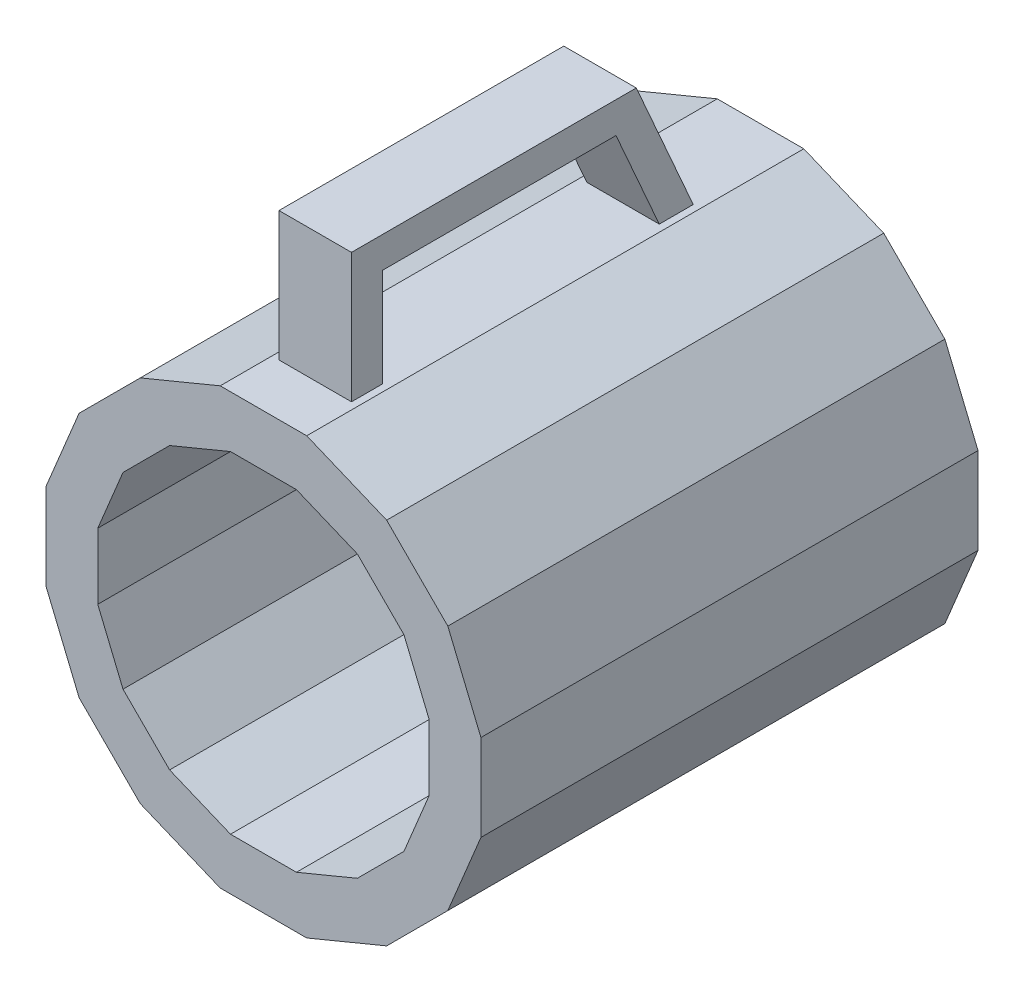
SolidWorks part; units mm, degrees
material "1060 Alloy"
ref_plane "Front Plane" through (0, 0, 0) normal (0, 0, 1) x (1, 0, 0)
ref_plane "Top Plane" through (0, 0, 0) normal (0, 1, 0) x (1, 0, 0)
ref_plane "Right Plane" through (0, 0, 0) normal (1, 0, 0) x (0, 0, -1)
sketch "Sketch1" plane through (0, 0, 0) normal (0, 0, 1) x (1, 0, 0)
  line L0 (-42, 8.3543) -> (-42, -8.3543)
  line L1 (35.6059, 23.7911) -> (23.7911, 35.6059)
  line L2 (23.7911, 35.6059) -> (8.3543, 42)
  line L3 (8.3543, 42) -> (-8.3543, 42)
  line L4 (-8.3543, 42) -> (-23.7911, 35.6059)
  line L5 (-23.7911, 35.6059) -> (-35.6059, 23.7911)
  line L6 (-35.6059, 23.7911) -> (-42, 8.3543)
  line L7 (-42, -8.3543) -> (-35.6059, -23.7911)
  line L8 (-35.6059, -23.7911) -> (-23.7911, -35.6059)
  line L9 (-23.7911, -35.6059) -> (-8.3543, -42)
  line L10 (-8.3543, -42) -> (8.3543, -42)
  line L11 (8.3543, -42) -> (23.7911, -35.6059)
  line L12 (23.7911, -35.6059) -> (35.6059, -23.7911)
  line L13 (35.6059, -23.7911) -> (42, -8.3543)
  line L14 (42, -8.3543) -> (42, 8.3543)
  line L15 (42, 8.3543) -> (35.6059, 23.7911)
  line L17 (18.1265, 27.1283) -> (6.3652, 32)
  line L18 (6.3652, 32) -> (-6.3652, 32)
  line L19 (-6.3652, 32) -> (-18.1265, 27.1283)
  line L20 (-18.1265, 27.1283) -> (-27.1283, 18.1265)
  line L21 (-27.1283, 18.1265) -> (-32, 6.3652)
  line L22 (-32, 6.3652) -> (-32, -6.3652)
  line L23 (-32, -6.3652) -> (-27.1283, -18.1265)
  line L24 (-27.1283, -18.1265) -> (-18.1265, -27.1283)
  line L25 (-18.1265, -27.1283) -> (-6.3652, -32)
  line L26 (-6.3652, -32) -> (6.3652, -32)
  line L27 (6.3652, -32) -> (18.1265, -27.1283)
  line L28 (18.1265, -27.1283) -> (27.1283, -18.1265)
  line L29 (27.1283, -18.1265) -> (32, -6.3652)
  line L30 (32, -6.3652) -> (32, 6.3652)
  line L31 (32, 6.3652) -> (27.1283, 18.1265)
  line L32 (27.1283, 18.1265) -> (18.1265, 27.1283)
  circle A0 centre (0, 0) radius 42 construction
  circle A2 centre (0, 0) radius 42 construction
  circle A3 centre (0, 0) radius 32 construction
  dimension "D1" = 64
  dimension "D3" = 84
extrude "Boss-Extrude1" add sketch "Sketch1" along normal blind 10 contours L31 L32 L17 L18 L19 L20 L21 L22 L23 L24 L25 L26 L27 L28 L29 L30 | L14 L15 L1 L2 L3 L4 L5 L6 L0 L7 L8 L9 L10 L11 L12 L13 L32 L31 L30 L29 L28 L27 L26 L25 L24 L23 L22 L21 L20 L19 L18 L17 region at (-37.7054, 15.6181, 0) region at (0, 0, 0)
extrude "Boss-Extrude2" add sketch "Sketch1<5>" along normal blind 86 from surface contours L14 L15 L1 L2 L3 L4 L5 L6 L0 L7 L8 L9 L10 L11 L12 L13 L32 L31 L30 L29 L28 L27 L26 L25 L24 L23 L22 L21 L20 L19 L18 L17 region at (-37.7054, 15.6181, 0) starting at face at (0, 0, 10)
sketch "Sketch1<5>" plane through (0, 0, 0) normal (0, 0, 1) x (1, 0, 0) same geometry as "Sketch1"
sketch "Sketch3" plane through (0, 0, 0) normal (1, 0, 0) x (0, 0, -1)
  line L0 (-86, 42) -> (-86, 67)
  line L1 (-96, 42) -> (0, 42) construction
  line L2 (-86, 67) -> (-31, 67)
  line L3 (-31, 67) -> (-20, 42)
  line L4 (0, 35.6059) -> (0, 42) construction
  line L5 (-80, 42) -> (-80, 61)
  line L6 (-80, 61) -> (-34.9151, 61)
  line L7 (-34.9151, 61) -> (-26.5551, 42)
  line L8 (-80, 42) -> (-86, 42)
  line L9 (-20, 42) -> (-26.5551, 42)
  line L10 (-34.9151, 61) -> (-25.4919, 39.5836) construction
  dimension "D1" = 10
  dimension "D2" = 25
  dimension "D3" = 20
  dimension "D4" = 55
  dimension "D5" = 6
extrude "Boss-Extrude3" add sketch "Sketch3" along normal mid plane 14
